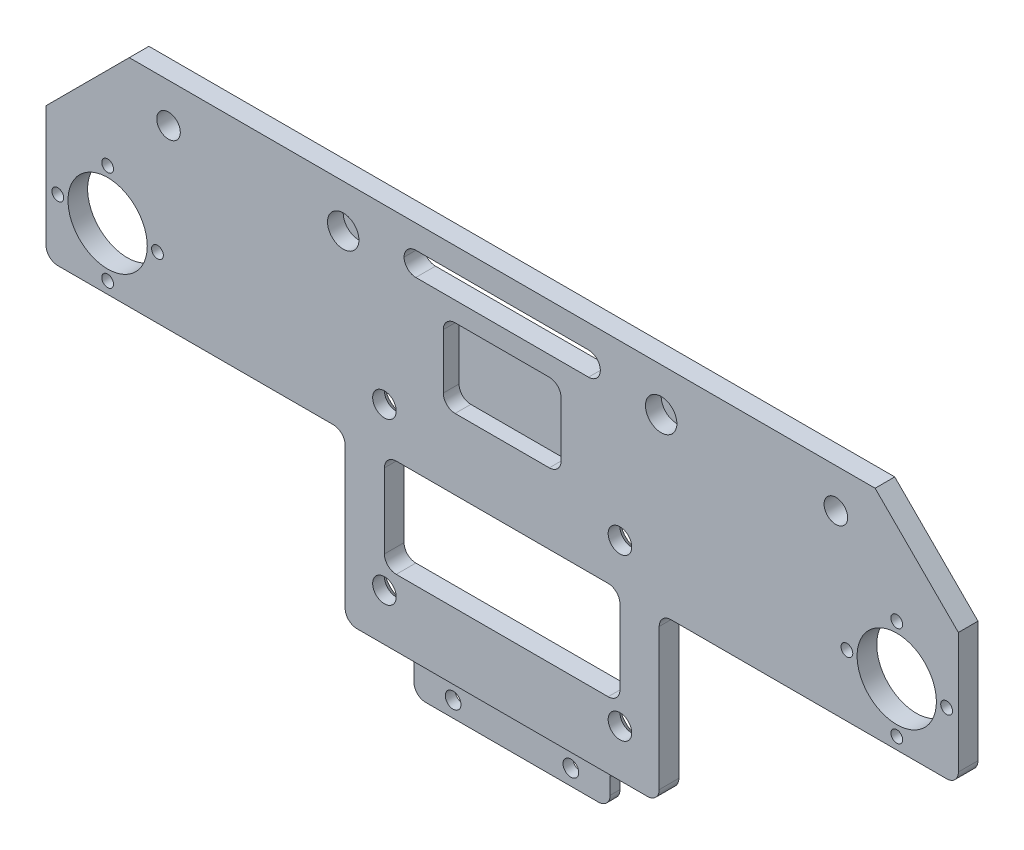
SolidWorks part; units mm, degrees
ref_plane "Plan de face" through (0, 0, 0) normal (0, 0, 1) x (1, 0, 0)
ref_plane "Plan de dessus" through (0, 0, 0) normal (0, 1, 0) x (1, 0, 0)
ref_plane "Plan de droite" through (0, 0, 0) normal (1, 0, 0) x (0, 0, -1)
sketch "Esquisse2" plane through (0, 0, 0) normal (0, 0, 1) x (1, 0, 0)
  line L2 (-95, 107) -> (95, 107) construction
  line L3 (-30, 52) -> (30, 52)
  line L4 (-30, 52) -> (-30, 27)
  line L5 (-40, 10) -> (-25, 10)
  line L6 (-40, 10) -> (-40, 52)
  line L7 (40, 10) -> (40, 52)
  line L8 (-30, 27) -> (30, 27)
  line L9 (30, 52) -> (30, 27)
  line L10 (25, 10) -> (40, 10)
  line L11 (-95, 107) -> (95, 107)
  line L12 (-25, 10) -> (-25, 0)
  line L13 (-25, 0) -> (25, 0)
  line L14 (25, 10) -> (25, 0)
  line L15 (95, 107) -> (116.2132, 85.7868)
  line L16 (-95, 107) -> (-116.2132, 85.7868)
  line L17 (-116.2132, 85.7868) -> (-116.2132, 52)
  line L18 (-116.2132, 52) -> (-40, 52)
  line L19 (40, 52) -> (116.2132, 52)
  line L20 (116.2132, 52) -> (116.2132, 85.7868)
  circle A0 centre (-30, 63) radius 3
  circle A2 centre (-30, 22) radius 3
  circle A3 centre (30, 22) radius 3
  circle A4 centre (30, 63) radius 3
  dimension "D14" = 6
  dimension "D15" = 6
  dimension "D16" = 6
  dimension "D17" = 6
  dimension "D2" = 55
  dimension "D3" = 30
  dimension "D4" = 60
  dimension "D5" = 25
  dimension "D6" = 17
  dimension "D7" = 30
  dimension "D8" = 80
  dimension "D9" = 0
  dimension "D10" = 190
  dimension "D11" = 50
  dimension "D12" = 10
  dimension "D13" = 15
  dimension "D18" = 60
  dimension "D19" = 11
  dimension "D20" = 11
  dimension "D21" = 0
  dimension "D22" = 0
  dimension "D23" = 0
  dimension "D24" = 5
  dimension "D25" = 5
  dimension "D26" = 135
  dimension "D27" = 135
  dimension "D28" = 25
  dimension "D29" = 30
  dimension "D30" = 116.2132
extrude "Boss.-Extru.2" add sketch "Esquisse2" along normal blind 5
sketch "Esquisse3" plane through (0, 0, 5) normal (0, 0, 1) x (1, 0, 0)
  line L1 (-25, 10) -> (25, 10)
  line L2 (-25, 10) -> (-25, 0)
  line L3 (-25, 0) -> (25, 0)
  line L4 (25, 10) -> (25, 0)
extrude "Enlèv. mat.-Extru.1" cut sketch "Esquisse3" against normal blind 2.5
sketch "Esquisse4" plane through (0, 0, 5) normal (0, 0, 1) x (1, 0, 0)
  line L1 (95, 107) -> (-95, 107) construction
  line L8 (-25, 101) -> (25, 101)
  line L9 (-25, 101) -> (-25, 95)
  line L10 (-25, 95) -> (25, 95)
  line L11 (25, 101) -> (25, 95)
  dimension "D1" = 6
  dimension "D5" = 50
  dimension "D6" = 6
  dimension "D7" = 25
extrude "Enlèv. mat.-Extru.2" cut sketch "Esquisse4" against normal through all
sketch "Esquisse5" plane through (0, 0, 5) normal (0, 0, 1) x (1, 0, 0)
  line L0 (-25, 95) -> (25, 95) construction
  line L1 (-15, 90) -> (15, 90)
  line L2 (-15, 90) -> (-15, 70)
  line L3 (-15, 70) -> (15, 70)
  line L4 (15, 90) -> (15, 70)
  dimension "D1" = 5
  dimension "D2" = 20
  dimension "D3" = 30
  dimension "D4" = 15
extrude "Enlèv. mat.-Extru.3" cut sketch "Esquisse5" against normal blind 4
chamfer "Chanfrein1" distance 2 angle 45 4 edges at (33, 22, 0) (33, 63, 0) (-27, 63, 0) (-27, 22, 0)
sketch "Esquisse6" plane through (0, 0, 5) normal (0, 0, 1) x (1, 0, 0)
  line L3 (95, 107) -> (-95, 107) construction
  circle A0 centre (-40.5, 96) radius 4
  circle A1 centre (40.5, 96) radius 4
  dimension "D1" = 8
  dimension "D2" = 8
  dimension "D7" = 11
  dimension "D3" = 40.5
  dimension "D4" = 40.5
  dimension "D6" = 11
extrude "Enlèv. mat.-Extru.4" cut sketch "Esquisse6" against normal blind 4
sketch "Esquisse7" plane through (0, 0, 5) normal (0, 0, 1) x (1, 0, 0)
  line L0 (95, 107) -> (-95, 107) construction
  line L2 (-15, 90) -> (-15, 70) construction
  line L4 (15, 70) -> (15, 90) construction
  circle A1 centre (-85, 97) radius 3
  circle A2 centre (85, 97) radius 3
  dimension "D8" = 6
  dimension "D9" = 6
  dimension "D1" = 10
  dimension "D2" = 70
  dimension "D3" = 10
  dimension "D4" = 70
extrude "Enlèv. mat.-Extru.5" cut sketch "Esquisse7" against normal through all
sketch "Esquisse8" plane through (0, 0, 2.5) normal (0, 0, 1) x (1, 0, 0)
  line L0 (-25, 0) -> (25, 0) construction
  line L1 (-25, 10) -> (-25, 0) construction
  line L2 (25, 0) -> (25, 10) construction
  circle A0 centre (-15, 4) radius 2
  circle A1 centre (15, 4) radius 2
  dimension "D1" = 4
  dimension "D2" = 4
  dimension "D3" = 4
  dimension "D4" = 4
  dimension "D5" = 10
  dimension "D6" = 10
extrude "Enlèv. mat.-Extru.6" cut sketch "Esquisse8" against normal through all
fillet "Congé2" radius 3 22 edges at (30, 52, 2.5) (-30, 27, 2.5) (30, 27, 2.5) (-25, 95, 2.5) (25, 95, 2.5) (25, 101, 2.5) (-25, 101, 2.5) (-30, 52, 2.5) (116.2132, 52, 2.5) (-40, 10, 2.5) (40, 10, 2.5) (-116.2132, 52, 2.5) (-15, 90, 3) (-15, 70, 3) (15, 70, 3) (15, 90, 3) (40, 52, 2.5) (-40, 52, 2.5) (-25, 10, 1.25) (25, 10, 1.25) (25, 0, 1.25) (-25, 0, 1.25)
sketch "Esquisse9" plane through (0, 0, 5) normal (0, 0, 1) x (1, 0, 0)
  line L0 (43, 52) -> (113.2132, 52) construction
  line L1 (116.2132, 55) -> (116.2132, 85.7868) construction
  line L2 (-116.2132, 85.7868) -> (-116.2132, 55) construction
  line L3 (-113.2132, 52) -> (-43, 52) construction
  circle A0 centre (100.5132, 67.7) radius 10.1
  circle A1 centre (113.2132, 67.7) radius 1.5
  circle A2 centre (100.5132, 80.4) radius 1.5
  circle A3 centre (87.8132, 67.7) radius 1.5
  circle A4 centre (100.5132, 55) radius 1.5
  circle A5 centre (-100.5132, 67.7) radius 10.1
  circle A6 centre (-87.8132, 67.7) radius 1.5
  circle A7 centre (-100.5132, 80.4) radius 1.5
  circle A8 centre (-113.2132, 67.7) radius 1.5
  circle A9 centre (-100.5132, 55) radius 1.5
  dimension "D5" = 20.2
  dimension "D6" = 3
  dimension "D13" = 20.2
  dimension "D14" = 3
  dimension "D1" = 12.7
  dimension "D2" = 12.7
  dimension "D3" = 12.7
  dimension "D4" = 12.7
  dimension "D7" = 3
  dimension "D8" = 3
  dimension "D9" = 12.7
  dimension "D10" = 12.7
  dimension "D11" = 12.7
  dimension "D12" = 12.7
  dimension "D15" = 3
  dimension "D16" = 3
extrude "Enlèv. mat.-Extru.7" cut sketch "Esquisse9" against normal through all
